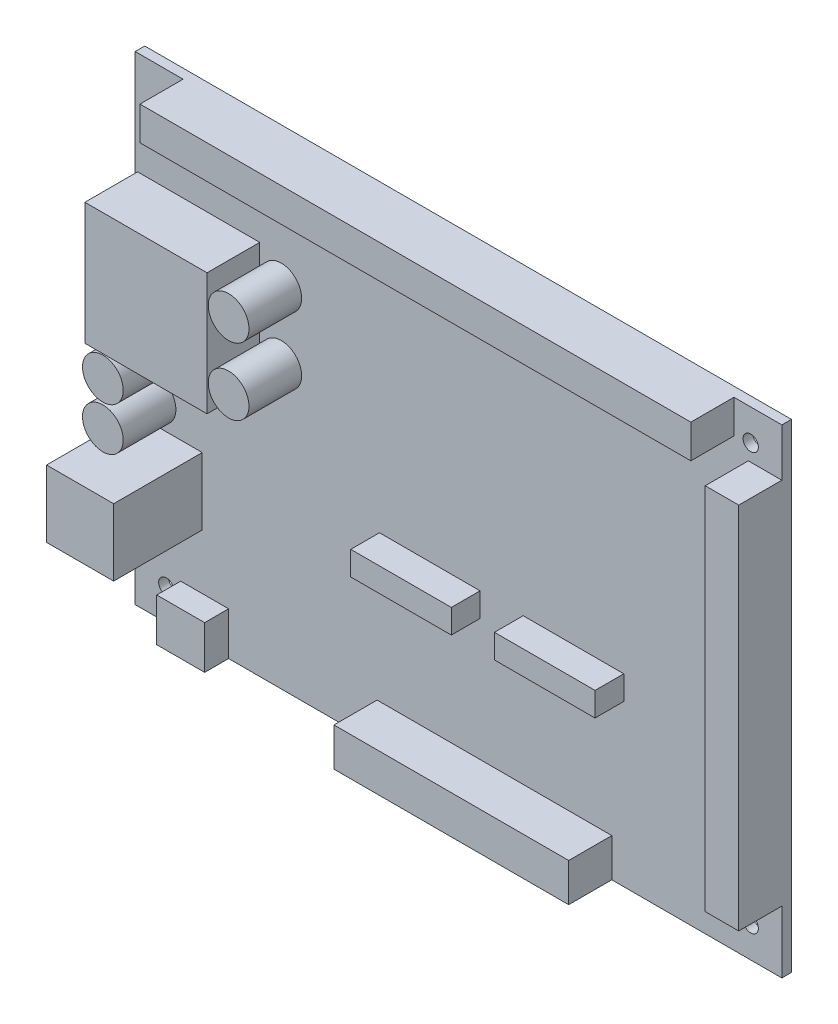
SolidWorks part; units mm, degrees
ref_plane "前视基准面" through (0, 0, 0) normal (0, 0, 1) x (1, 0, 0)
ref_plane "上视基准面" through (0, 0, 0) normal (0, 1, 0) x (1, 0, 0)
ref_plane "右视基准面" through (0, 0, 0) normal (1, 0, 0) x (0, 0, -1)
other "Configuration Table"
sketch "草图1" plane through (0, 0, 0) normal (0, 0, 1) x (1, 0, 0)
  line L0 (6.5, -6.5) -> (128.5, -6.5) construction
  line L1 (0, 0) -> (135, 0)
  line L2 (0, 0) -> (0, -100)
  line L3 (0, -100) -> (135, -100)
  line L4 (135, 0) -> (135, -100)
  line L5 (6.5, -6.5) -> (6.5, -93.5) construction
  line L6 (6.5, -93.5) -> (128.5, -93.5) construction
  line L7 (128.5, -93.5) -> (128.5, -6.5) construction
  line L8 (67.5, 0) -> (67.5, -100) construction
  line L9 (0, -50) -> (135, -50) construction
  circle A0 centre (6.5, -6.5) radius 1.6
  circle A1 centre (128.5, -6.5) radius 1.6
  circle A2 centre (6.5, -93.5) radius 1.6
  circle A3 centre (128.5, -93.5) radius 1.6
  point P17 (6.5, -50)
  point P18 (67.5, -6.5)
  dimension "D5" = 3.2
  dimension "D1" = 135
  dimension "D2" = 100
  dimension "D3" = 122
  dimension "D4" = 87
extrude "凸台-拉伸1" add sketch "草图1" along normal blind 2
sketch "草图2" plane through (0, 0, 2) normal (0, 0, 1) x (1, 0, 0)
  line L0 (0, -100) -> (135, -100) construction
  line L1 (9.5, -100) -> (19.5, -100)
  line L2 (9.5, -100) -> (9.5, -91)
  line L3 (9.5, -91) -> (19.5, -91)
  line L4 (19.5, -100) -> (19.5, -91)
  line L5 (0, 0) -> (0, -100) construction
  dimension "D1" = 19.5
  dimension "D2" = 10
  dimension "D3" = 9
extrude "凸台-拉伸2" add sketch "草图2" along normal blind 5
sketch "草图3" plane through (0, 0, 2) normal (0, 0, 1) x (1, 0, 0)
  line L0 (135, 0) -> (0, 0) construction
  line L1 (10, 0) -> (125, 0)
  line L2 (10, 0) -> (10, -7)
  line L3 (10, -7) -> (125, -7)
  line L4 (125, 0) -> (125, -7)
  line L5 (67.5, -100) -> (67.5, 0) construction
  line L8 (19.5, -100) -> (135, -100) construction
  dimension "D1" = 115
  dimension "D2" = 7
extrude "凸台-拉伸3" add sketch "草图3" along normal blind 9
sketch "草图4" plane through (0, 0, 2) normal (0, 0, 1) x (1, 0, 0)
  line L0 (135, -100) -> (135, 0) construction
  line L1 (128, -10) -> (135, -10)
  line L2 (128, -10) -> (128, -87)
  line L3 (128, -87) -> (135, -87)
  line L4 (135, -10) -> (135, -87)
  line L5 (19.5, -100) -> (135, -100) construction
  dimension "D1" = 90
  dimension "D2" = 7
  dimension "D3" = 77
extrude "凸台-拉伸4" add sketch "草图4" along normal blind 9
sketch "草图5" plane through (0, 0, 2) normal (0, 0, 1) x (1, 0, 0)
  line L0 (19.5, -100) -> (135, -100) construction
  line L1 (50.5, -100) -> (99.5, -100)
  line L2 (50.5, -100) -> (50.5, -92)
  line L3 (50.5, -92) -> (99.5, -92)
  line L4 (99.5, -100) -> (99.5, -92)
  line L5 (135, -100) -> (135, -87) construction
  dimension "D1" = 49
  dimension "D2" = 8
  dimension "D3" = 84.5
extrude "凸台-拉伸5" add sketch "草图5" along normal blind 9
sketch "草图6" plane through (0, 0, 2) normal (0, 0, 1) x (1, 0, 0)
  line L1 (0.5, -21.5) -> (26, -21.5)
  line L2 (0.5, -21.5) -> (0.5, -47)
  line L3 (0.5, -47) -> (26, -47)
  line L4 (26, -21.5) -> (26, -47)
  line L5 (0, 0) -> (0, -100) construction
  line L6 (125, 0) -> (10, 0) construction
  line L7 (30.5, -27.25) -> (30.5, -41.25) construction
  line L8 (26, -34.25) -> (30.5, -34.25) construction
  line L9 (0, -65.5) -> (14, -65.5)
  line L10 (0, -65.5) -> (0, -79.5)
  line L11 (0, -79.5) -> (14, -79.5)
  line L12 (14, -65.5) -> (14, -79.5)
  circle A0 centre (30.5, -27.25) radius 4.25
  circle A1 centre (30.5, -41.25) radius 4.25
  circle A2 centre (4.25, -60.5) radius 4.25
  circle A3 centre (4.25, -51.5) radius 4.25
  dimension "D4" = 8.5
  dimension "D7" = 5
  dimension "D8" = 4.5
  dimension "D10" = 9
  dimension "D1" = 25.5
  dimension "D2" = 0.5
  dimension "D3" = 47
  dimension "D5" = 14
  dimension "D6" = 14
  dimension "D9" = 4.5
extrude "凸台-拉伸6" add sketch "草图6" along normal blind 11 contours L1 L4 L3 L2
extrude "凸台-拉伸10" add sketch "草图6<5>" along normal blind 11 contours A0 | A1 | A3 | A2
sketch "草图6<5>" plane through (0, 0, 2) normal (0, 0, 1) x (1, 0, 0) same geometry as "草图6"
extrude "凸台-拉伸11" add sketch "草图6<6>" along normal blind 18.5 contours L12 L11 L10 L9
sketch "草图6<6>" plane through (0, 0, 2) normal (0, 0, 1) x (1, 0, 0) same geometry as "草图6"
sketch "草图8" plane through (0, 0, 2) normal (0, 0, 1) x (1, 0, 0)
  line L0 (99.5, -100) -> (135, -100) construction
  line L1 (51, -61.5) -> (72, -61.5)
  line L2 (51, -61.5) -> (51, -66.5)
  line L3 (51, -66.5) -> (72, -66.5)
  line L4 (72, -61.5) -> (72, -66.5)
  line L5 (81, -61.5) -> (102, -61.5)
  line L6 (81, -61.5) -> (81, -66.5)
  line L7 (81, -66.5) -> (102, -66.5)
  line L8 (102, -61.5) -> (102, -66.5)
  line L10 (135, -87) -> (135, -10) construction
  dimension "D1" = 38.5
  dimension "D2" = 51
  dimension "D3" = 21
  dimension "D4" = 21
  dimension "D5" = 5
  dimension "D6" = 54
extrude "凸台-拉伸12" add sketch "草图8" along normal blind 6
sketch "草图9" plane through (0, -100, 0) normal (0, -1, 0) x (1, 0, 0)
  line L4 (0, 2) -> (14, 2) construction
  line L5 (10.8, 5.7) -> (18.2, 5.7)
  line L6 (10.8, 5.7) -> (10.8, 2.5)
  line L7 (10.8, 2.5) -> (18.2, 2.5)
  line L8 (18.2, 5.7) -> (18.2, 2.5)
  line L9 (9.5, 7) -> (9.5, 2) construction
  line L10 (19.5, 7) -> (19.5, 2) construction
  line L11 (9.5, 7) -> (19.5, 7) construction
  dimension "D1" = 0.5
  dimension "D2" = 1.3
  dimension "D3" = 1.3
  dimension "D4" = 1.3
extrude "切除-拉伸1" cut sketch "草图9" against normal blind 6
